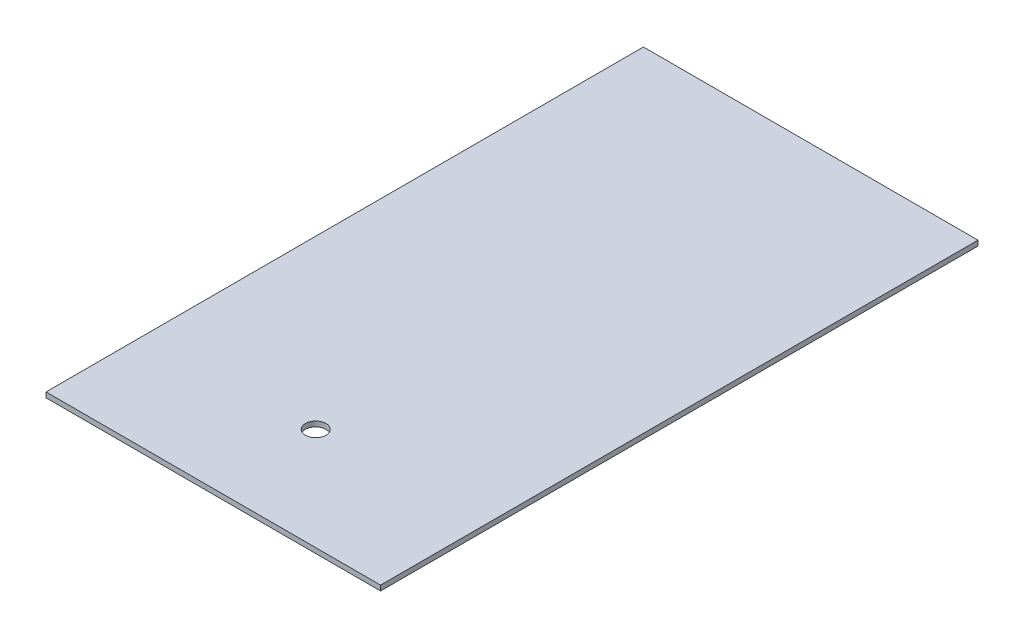
SolidWorks part; units mm, degrees
ref_plane "Front Plane" through (0, 0, 0) normal (0, 0, 1) x (1, 0, 0)
ref_plane "Top Plane" through (0, 0, 0) normal (0, 1, 0) x (1, 0, 0)
ref_plane "Right Plane" through (0, 0, 0) normal (1, 0, 0) x (0, 0, -1)
sketch "Sketch1" plane through (0, 0, 0) normal (0, 1, 0) x (1, 0, 0)
  line L1 (0, 0) -> (196, 0)
  line L2 (0, 0) -> (0, 350)
  line L3 (0, 350) -> (196, 350)
  line L4 (196, 0) -> (196, 350)
  dimension "D1" = 350
  dimension "D2" = 196
extrude "Boss-Extrude1" add sketch "Sketch1" along normal blind 3
hole_wizard "Ø12.0mm Dowel Hole1" positions "Sketch2" profile "Sketch3" hole size "Ø12.0" standard "ANSI Metric" end condition up to next
sketch "Sketch2" plane through (0, 3, 0) normal (0, 1, 0) x (1, 0, 0)
  point P0 (98, 60)
sketch "Sketch3" plane through (98, 3, -60) normal (1, 0, 0) x (0, 0, 1)
  line L0 (0, 0) -> (0, 3)
  line L1 (0, 3) -> (6, 3)
  line L2 (6, 3) -> (6, 0)
  line L5 (6, 0) -> (0, 0)
  line L11 (0, -6.35) -> (0, 107.95) construction
  dimension "Thru Hole Dia." = 12
  dimension "Thru Hole Depth" = 3
